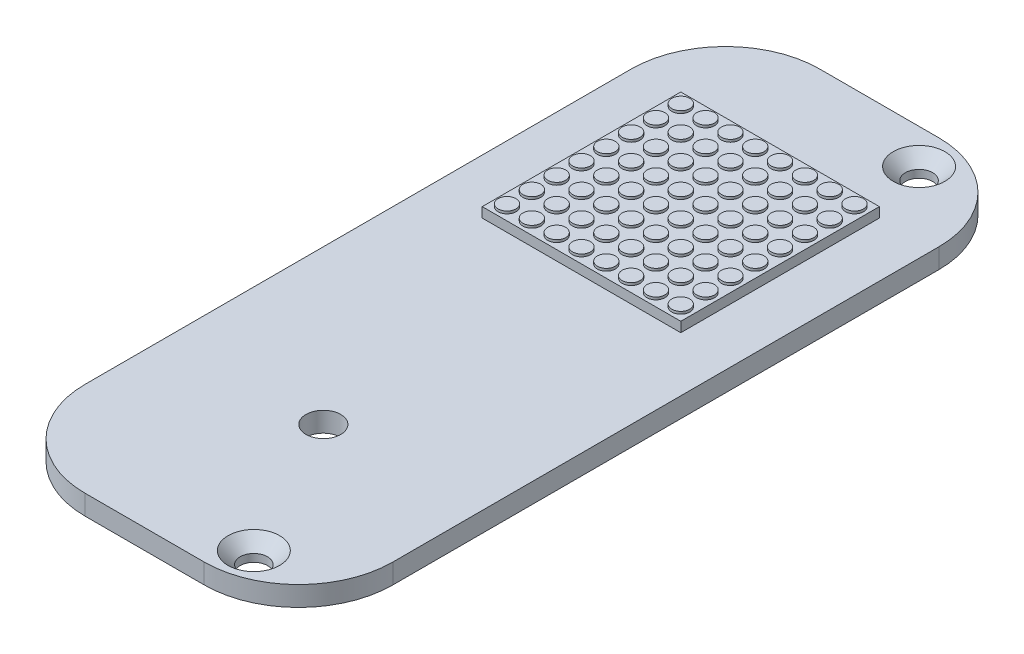
SolidWorks part; units mm, degrees
ref_plane "Front Plane" through (0, 0, 0) normal (0, 0, 1) x (1, 0, 0)
ref_plane "Top Plane" through (0, 0, 0) normal (0, 1, 0) x (1, 0, 0)
ref_plane "Right Plane" through (0, 0, 0) normal (1, 0, 0) x (0, 0, -1)
sketch "Sketch1" plane through (0, 0, 0) normal (0, 1, 0) x (1, 0, 0)
  line L0 (0, 14) -> (0, 54) construction
  line L1 (-12, -74) -> (12, -74)
  line L2 (-31, -55) -> (-31, 55)
  line L3 (-12, 74) -> (12, 74)
  line L4 (31, -55) -> (31, 55)
  line L5 (-31, -74) -> (31, 74) construction
  line L6 (-31, 74) -> (31, -74) construction
  line L7 (-20, 14) -> (20, 14)
  line L8 (-20, 14) -> (-20, 54)
  line L9 (-20, 54) -> (20, 54)
  line L10 (20, 14) -> (20, 54)
  line L11 (-20, 14) -> (20, 54) construction
  line L12 (-20, 54) -> (20, 14) construction
  line L13 (20, 34) -> (-20, 34) construction
  circle A0 centre (-17.5, 51.5) radius 1.8
  circle A1 centre (-17.5, 46.5) radius 1.8
  circle A2 centre (-17.5, 41.5) radius 1.8
  circle A3 centre (-17.5, 36.5) radius 1.8
  circle A4 centre (-17.5, 31.5) radius 1.8
  circle A5 centre (-17.5, 26.5) radius 1.8
  circle A6 centre (-17.5, 21.5) radius 1.8
  circle A7 centre (-17.5, 16.5) radius 1.8
  circle A8 centre (-12.5, 46.5) radius 1.8
  circle A9 centre (-12.5, 41.5) radius 1.8
  circle A10 centre (-12.5, 36.5) radius 1.8
  circle A11 centre (-12.5, 31.5) radius 1.8
  circle A12 centre (-12.5, 26.5) radius 1.8
  circle A13 centre (-12.5, 21.5) radius 1.8
  circle A14 centre (-12.5, 16.5) radius 1.8
  circle A15 centre (-7.5, 46.5) radius 1.8
  circle A16 centre (-7.5, 41.5) radius 1.8
  circle A17 centre (-7.5, 36.5) radius 1.8
  circle A18 centre (-7.5, 31.5) radius 1.8
  circle A19 centre (-7.5, 26.5) radius 1.8
  circle A20 centre (-7.5, 21.5) radius 1.8
  circle A21 centre (-7.5, 16.5) radius 1.8
  circle A22 centre (-2.5, 46.5) radius 1.8
  circle A23 centre (-2.5, 41.5) radius 1.8
  circle A24 centre (-2.5, 36.5) radius 1.8
  circle A25 centre (-2.5, 31.5) radius 1.8
  circle A26 centre (-2.5, 26.5) radius 1.8
  circle A27 centre (-2.5, 21.5) radius 1.8
  circle A28 centre (-2.5, 16.5) radius 1.8
  circle A29 centre (2.5, 46.5) radius 1.8
  circle A30 centre (2.5, 41.5) radius 1.8
  circle A31 centre (2.5, 36.5) radius 1.8
  circle A32 centre (2.5, 31.5) radius 1.8
  circle A33 centre (2.5, 26.5) radius 1.8
  circle A34 centre (2.5, 21.5) radius 1.8
  circle A35 centre (2.5, 16.5) radius 1.8
  circle A36 centre (7.5, 46.5) radius 1.8
  circle A37 centre (7.5, 41.5) radius 1.8
  circle A38 centre (7.5, 36.5) radius 1.8
  circle A39 centre (7.5, 31.5) radius 1.8
  circle A40 centre (7.5, 26.5) radius 1.8
  circle A41 centre (7.5, 21.5) radius 1.8
  circle A42 centre (7.5, 16.5) radius 1.8
  circle A43 centre (12.5, 46.5) radius 1.8
  circle A44 centre (12.5, 41.5) radius 1.8
  circle A45 centre (12.5, 36.5) radius 1.8
  circle A46 centre (12.5, 31.5) radius 1.8
  circle A47 centre (12.5, 26.5) radius 1.8
  circle A48 centre (12.5, 21.5) radius 1.8
  circle A49 centre (12.5, 16.5) radius 1.8
  circle A50 centre (17.5, 46.5) radius 1.8
  circle A51 centre (17.5, 41.5) radius 1.8
  circle A52 centre (17.5, 36.5) radius 1.8
  circle A53 centre (17.5, 31.5) radius 1.8
  circle A54 centre (17.5, 26.5) radius 1.8
  circle A55 centre (17.5, 21.5) radius 1.8
  circle A56 centre (17.5, 16.5) radius 1.8
  circle A57 centre (-12.5, 51.5) radius 1.8
  circle A58 centre (-7.5, 51.5) radius 1.8
  circle A59 centre (-2.5, 51.5) radius 1.8
  circle A60 centre (2.5, 51.5) radius 1.8
  circle A61 centre (7.5, 51.5) radius 1.8
  circle A62 centre (12.5, 51.5) radius 1.8
  circle A63 centre (17.5, 51.5) radius 1.8
  circle A64 centre (0, -38) radius 3.5
  arc A65 (-31, -55) -> (-12, -74) centre (-12, -55) ccw
  arc A66 (12, -74) -> (31, -55) centre (12, -55) ccw
  arc A67 (31, 55) -> (12, 74) centre (12, 55) ccw
  arc A68 (-31, 55) -> (-12, 74) centre (-12, 55) cw
  point P0 (0, 0)
  point P6 (0, 34)
  dimension "D7" = 8
  dimension "D14" = 7
  dimension "D15" = 3.6
  dimension "D17" = 19
  dimension "D1" = 148
  dimension "D2" = 62
  dimension "D3" = 40
  dimension "D4" = 11
  dimension "D5" = 20
  dimension "D6" = 40
  dimension "D9" = 2.5
  dimension "D10" = 2.5
  dimension "D11" = 2.5
  dimension "D12" = 2.5
  dimension "D13" = 38
  dimension "D16" = 31
  dimension "D8" = 8
extrude "Boss-Extrude1" add sketch "Sketch1" along normal blind 4 contours L1 L4 L3 L2 A64 L10 L7 L8 L9 region at (0, 0, 7.3243)
extrude "Boss-Extrude2" add sketch "Sketch1<5>" along normal blind 6 contours L7 L10 L9 L8 A63 A62 A61 A60 A59 A58 A57 A56 A55 A54 A53 A52 A51 A50 A49 A48 A47 A46 A45 A44 A43 A42 A41 region at (0, 0, -34)
sketch "Sketch1<5>" plane through (0, 0, 0) normal (0, 1, 0) x (1, 0, 0) same geometry as "Sketch1"
extrude "Boss-Extrude3" add sketch "Sketch1<6>" along normal blind 6.5 contours A16 | A9 | A8 | A15 | A57 | A0 | A1 | A2 | A3 | A4 | A5 | A6 | A7 | A14 | A13 | A12 | A11 | A10 | A17 | A18 | A19 | A20 | A21 | A28 | A27 | A25 | A26 | A24 | A23 | A22 | A59 | A58 | A60 | A29 | A30 | A37 | A36 | A61 | A62 | A43 | A50 | A63 | A51 | A44 | A45 | A38 | A31 | A32 | A39 | A46 | A53 | A52 | A54 | A55 | A56 | A49 | A48 | A47 | A40 | A33 | A34 | A41 | A42 | A35 region at (-17.5, 0, -51.5) region at (-17.5, 0, -46.5) region at (-17.5, 0, -41.5) region at (-17.5, 0, -36.5) region at (-17.5, 0, -31.5) region at (-17.5, 0, -26.5) region at (-17.5, 0, -21.5) region at (-17.5, 0, -16.5) region at (-12.5, 0, -46.5) region at (-12.5, 0, -41.5) region at (-12.5, 0, -36.5) region at (-12.5, 0, -31.5) region at (-12.5, 0, -26.5) region at (-12.5, 0, -21.5) region at (-12.5, 0, -16.5) region at (-7.5, 0, -46.5) region at (-7.5, 0, -41.5) region at (-7.5, 0, -36.5) region at (-7.5, 0, -31.5) region at (-7.5, 0, -26.5) region at (-7.5, 0, -21.5) region at (-7.5, 0, -16.5) region at (-2.5, 0, -46.5) region at (-2.5, 0, -41.5) region at (-2.5, 0, -36.5) region at (-2.5, 0, -31.5) region at (-2.5, 0, -26.5) region at (-2.5, 0, -21.5) region at (-2.5, 0, -16.5) region at (2.5, 0, -46.5) region at (2.5, 0, -41.5) region at (2.5, 0, -36.5) region at (2.5, 0, -31.5) region at (2.5, 0, -26.5) region at (2.5, 0, -21.5) region at (2.5, 0, -16.5) region at (7.5, 0, -46.5) region at (7.5, 0, -41.5) region at (7.5, 0, -36.5) region at (7.5, 0, -31.5) region at (7.5, 0, -26.5) region at (7.5, 0, -21.5) region at (7.5, 0, -16.5) region at (12.5, 0, -46.5) region at (12.5, 0, -41.5) region at (12.5, 0, -36.5) region at (12.5, 0, -31.5) region at (12.5, 0, -26.5) region at (12.5, 0, -21.5) region at (12.5, 0, -16.5) region at (17.5, 0, -46.5) region at (17.5, 0, -41.5) region at (17.5, 0, -36.5) region at (17.5, 0, -31.5) region at (17.5, 0, -26.5) region at (17.5, 0, -21.5) region at (17.5, 0, -16.5) region at (-12.5, 0, -51.5) region at (-7.5, 0, -51.5) region at (-2.5, 0, -51.5)
sketch "Sketch1<6>" plane through (0, 0, 0) normal (0, 1, 0) x (1, 0, 0) same geometry as "Sketch1"
sketch "Sketch5" plane through (0, 4, 0) normal (0, 1, 0) x (1, 0, 0)
  line L0 (15, -74) -> (15, -67) construction
  line L2 (-12, -74) -> (12, -74) construction
  line L3 (31, -55) -> (31, 55) construction
  line L4 (-33.7528, 0) -> (39.8836, 0) construction
  line L5 (15, 74) -> (15, 67) construction
  dimension "D1" = 7
  dimension "D2" = 16
hole_wizard "CSK for M5 Countersunk Flat Head1" positions "Sketch6" profile "Sketch7" countersink size "M5" standard "BSI" end condition up to next
sketch "Sketch6" plane through (0, 4, 0) normal (0, 1, 0) x (1, 0, 0)
  point P0 (15, 67)
  point P3 (15, -67)
sketch "Sketch7" plane through (15, 4, -67) normal (1, 0, 0) x (0, 0, 1)
  line L0 (0, 0) -> (0, 4)
  line L1 (0, 4) -> (2.75, 4)
  line L2 (2.75, 4) -> (2.75, 2.45)
  line L3 (2.75, 2.45) -> (5.2, 0)
  line L5 (5.2, 0) -> (0, 0)
  line L6 (-2.75, 2.45) -> (-5.2, 0) construction
  line L11 (0, -6.35) -> (0, 107.95) construction
  dimension "Thru Hole Dia." = 5.5
  dimension "Thru Hole Depth" = 4
  dimension "Near C'Sink Dia." = 10.4
  dimension "Near C'Sink Angle" = 90
